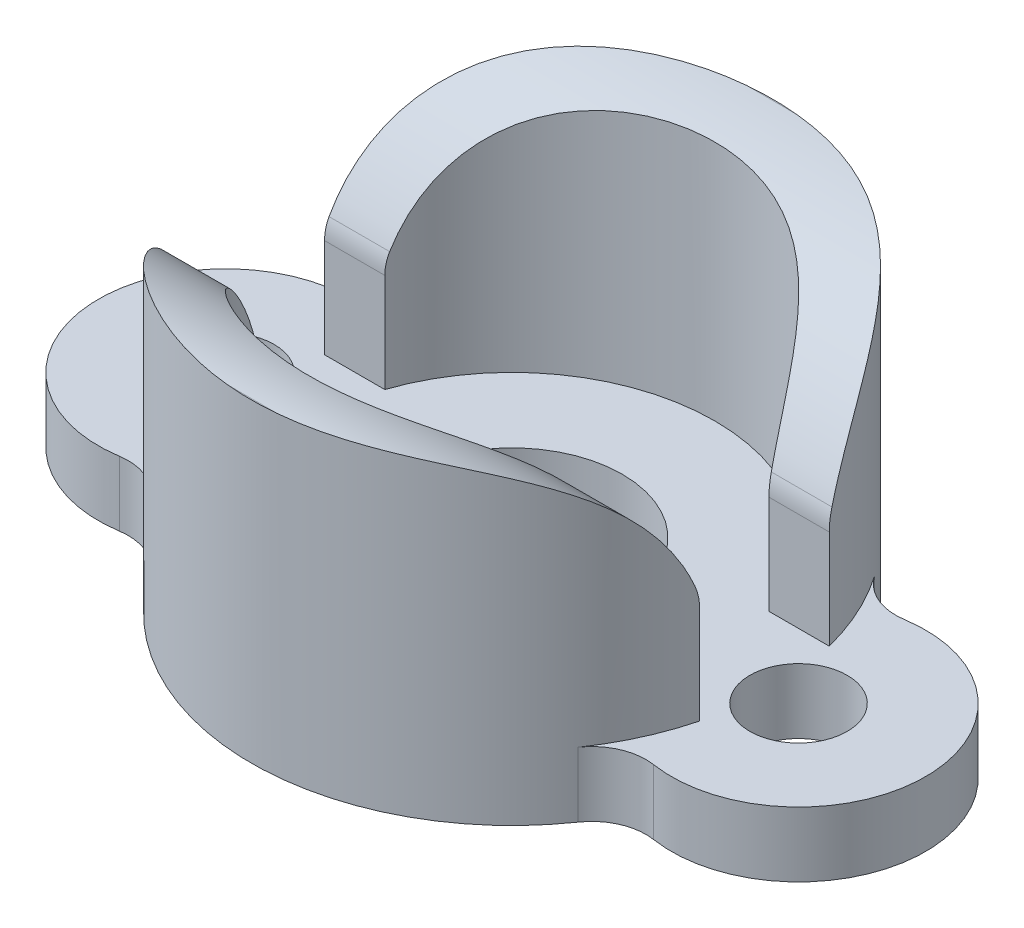
SolidWorks part; units mm, degrees
ref_plane "Front" through (0, 0, 0) normal (0, 0, 1) x (1, 0, 0)
ref_plane "Top" through (0, 0, 0) normal (0, 1, 0) x (1, 0, 0)
ref_plane "Right" through (0, 0, 0) normal (1, 0, 0) x (0, 0, -1)
sketch "Sketch1" plane through (0, 0, 0) normal (0, 1, 0) x (1, 0, 0)
  line L0 (0, 0) -> (6.731, 0) construction
  line L3 (0, 0) -> (-6.731, 0) construction
  arc A0 (6.2738, 2.9493) -> (6.2738, -2.9493) centre (6.731, 0) cw
  circle A1 centre (0, 0) radius 2.5912
  arc A2 (5.0347, 3.4819) -> (-5.0347, 3.4819) centre (0, 0) ccw
  arc A3 (-6.2738, -2.9493) -> (-6.2738, 2.9493) centre (-6.731, 0) cw
  arc A4 (-5.0347, -3.4819) -> (5.0347, -3.4819) centre (0, 0) ccw
  circle A5 centre (-6.731, 0) radius 1.143
  circle A6 centre (6.731, 0) radius 1.143
  arc A7 (-6.2738, -2.9493) -> (-5.0347, -3.4819) centre (-6.0792, -4.2043) cw
  arc A8 (-5.0347, 3.4819) -> (-6.2738, 2.9493) centre (-6.0792, 4.2043) cw
  arc A9 (6.2738, 2.9493) -> (5.0347, 3.4819) centre (6.0792, 4.2043) cw
  arc A10 (5.0347, -3.4819) -> (6.2738, -2.9493) centre (6.0792, -4.2043) cw
  dimension "D1" = 5.1824
  dimension "D3" = 2.9845
  dimension "D4" = 6.1214
  dimension "D6" = 6.731
  dimension "D7" = 2.286
  dimension "D9" = 2
  dimension "D8" = 6.1214
  dimension "D10" = 1.27
  dimension "D2" = 6.731
  dimension "D5" = 2
extrude "Boss-Extrude4" add sketch "Sketch1" along normal blind 1.524 contours A3 A0 A2 A1 region at (9.4858, 0, 0)
sketch "Sketch5" plane through (0, 1.524, 0) normal (0, 1, 0) x (1, 0, 0)
  circle A0 centre (0, 0) radius 6.1214
  circle A1 centre (0, 0) radius 4.7625
  dimension "D1" = 12.2428
  dimension "D2" = 9.525
extrude "Boss-Extrude6" add sketch "Sketch5" along normal blind 5.8674
sketch "Sketch6" plane through (0, 0, 0) normal (1, 0, 0) x (0, 0, -1)
  line L0 (-1.524, 1.524) -> (1.524, 1.524)
  line L1 (-0.9194, 1.524) -> (0.9194, 1.524) construction
  line L2 (-2.713, 1.524) -> (-6.1214, 1.524) construction
  line L3 (1.524, 1.524) -> (1.524, 3.8465)
  line L4 (0, 1.524) -> (0, 7.3914) construction
  line L5 (4.7625, 7.3914) -> (-4.7625, 7.3914) construction
  line L6 (6.1214, 7.3914) -> (-6.1214, 7.3914)
  line L7 (-1.524, 1.524) -> (-1.524, 3.8465)
  arc A0 (1.6088, 4.3028) -> (6.1214, 7.3914) centre (6.1073, 2.5711) cw
  arc A1 (1.524, 3.8465) -> (1.6088, 4.3028) centre (2.794, 3.8465) cw
  arc A2 (-1.524, 3.8465) -> (-1.6088, 4.3028) centre (-2.794, 3.8465) ccw
  arc A3 (-1.6088, 4.3028) -> (-6.1214, 7.3914) centre (-6.1073, 2.5711) ccw
  point P15 (1.524, 4.064)
  dimension "D3" = 1.27
  dimension "D1" = 1.524
  dimension "D2" = 2.54
extrude "Cut-Extrude1" cut sketch "Sketch6" against normal through all and the other way through all contours L0 L4 L6 A3 A2 L7 | L4 L0 L3 A1 A0 L6 region at (0, 5.0984, 1.331) region at (0, 5.0984, -1.331)
